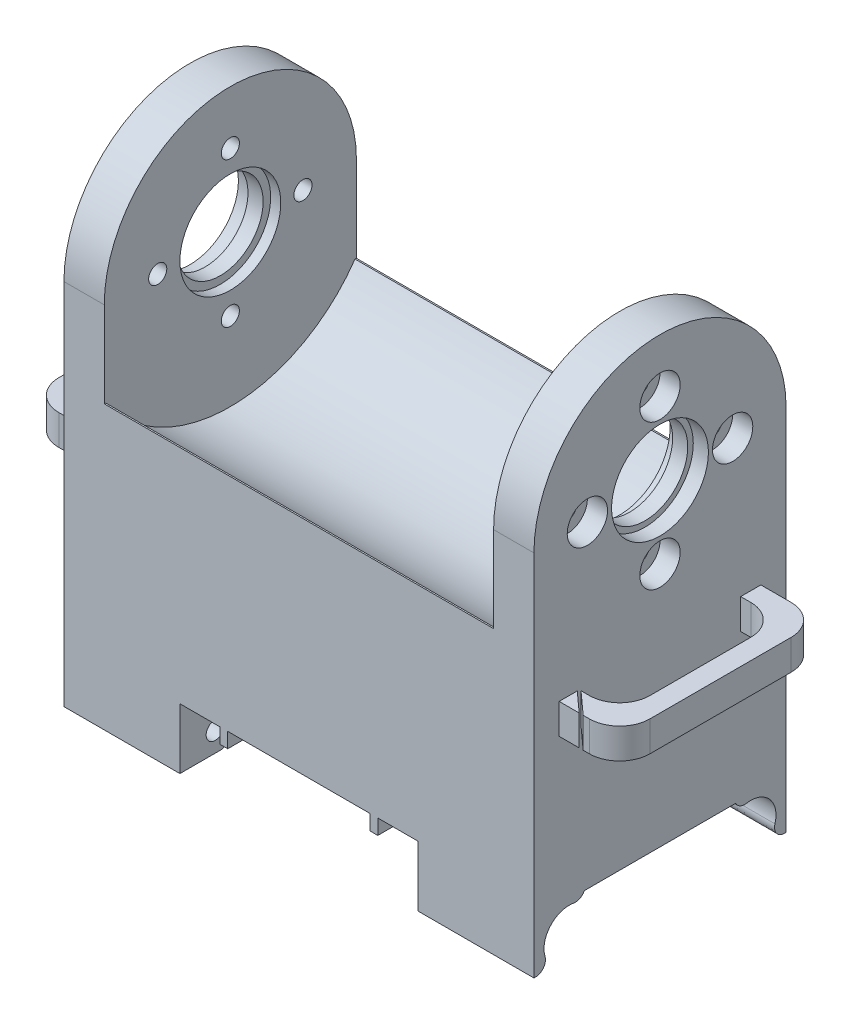
SolidWorks part; units mm, degrees
ref_plane "Front Plane" through (0, 0, 0) normal (0, 0, 1) x (1, 0, 0)
ref_plane "Top Plane" through (0, 0, 0) normal (0, 1, 0) x (1, 0, 0)
ref_plane "Right Plane" through (0, 0, 0) normal (1, 0, 0) x (0, 0, -1)
sketch "Sketch1" plane through (0, 0, 0) normal (1, 0, 0) x (0, 0, -1)
  line L0 (0, 45.2885) -> (0, -49.9038) construction
  line L1 (-47.1154, 0) -> (49.2308, 0) construction
  line L2 (-47.1154, -15) -> (49.2308, -15) construction
  line L3 (-7.5, -16) -> (7.5, -16)
  line L4 (-12.5, 28) -> (12.5, 28)
  line L5 (-12.5, 28) -> (-12.5, -21)
  line L6 (-12.5, -21) -> (-7.5, -21)
  line L7 (12.5, 28) -> (12.5, -21)
  line L8 (7.5, -21) -> (12.5, -21)
  line L9 (-7.5, -16) -> (-7.5, -21)
  line L11 (7.5, -16) -> (7.5, -21)
  point P11 (-12.5, -15)
  point P12 (-12.5, 3.5)
  dimension "D1" = 12.5
  dimension "D2" = 12.5
  dimension "D3" = 28
  dimension "D4" = 6
  dimension "D5" = 15
  dimension "D6" = 5
  dimension "D7" = 5
  dimension "D8" = 1
extrude "Boss-Extrude1" add sketch "Sketch1" along normal blind 4
sketch "Sketch3" plane through (0, 0, 0) normal (-1, 0, 0) x (0, 0, 1)
  line L0 (-12.5, -21) -> (-12.5, 28) construction
  line L1 (-12.5, -15) -> (12.5, -15)
  line L2 (-12.5, -15) -> (-12.5, 7)
  line L3 (-12.5, 7) -> (12.5, 7)
  line L4 (12.5, -15) -> (12.5, 7)
  line L5 (12.5, 28) -> (12.5, -21) construction
  line L6 (7.5, -16) -> (-7.5, -16) construction
  line L7 (-12.5, 28) -> (12.5, 28) construction
  dimension "D1" = 1
  dimension "D2" = 21
extrude "Boss-Extrude2" add sketch "Sketch3" along normal blind 19.3
fillet "Fillet1" 2 edges at (2, 28, 12.5) (2, 28, -12.5) type full round first side face at (-3.825, -0.25, 12.5) second side face at (-3.825, -0.25, -12.5) middle face at (2, 28, 0)
sketch "Sketch4" plane through (0, 0, 0) normal (-1, 0, 0) x (0, 0, 1)
  line L0 (-12.5, 15.5) -> (20.8842, 15.5) construction
  circle A0 centre (0, 15.5) radius 15
extrude "Cut-Extrude1" cut sketch "Sketch4" along normal up to next
sketch "Sketch5" plane through (4, 0, 0) normal (1, 0, 0) x (0, 0, -1)
  line L0 (-12.5, 15.5) -> (19.316, 15.5) construction
  circle A0 centre (0, 15.5) radius 4.25
  dimension "D1" = 8.5
extrude "Cut-Extrude2" cut sketch "Sketch5" against normal up to next
sketch "Sketch6" plane through (4, 0, 0) normal (1, 0, 0) x (0, 0, -1)
  circle A0 centre (0, 15.5) radius 4.8
  dimension "D1" = 9.6
extrude "Cut-Extrude3" cut sketch "Sketch6" against normal blind 1.5
sketch "Sketch7" plane through (0, 0, 0) normal (-1, 0, 0) x (0, 0, 1)
  circle A0 centre (0, 15.5) radius 5
  dimension "D1" = 10
extrude "Cut-Extrude4" cut sketch "Sketch7" against normal blind 1
sketch "Sketch8" plane through (4, 0, 0) normal (1, 0, 0) x (0, 0, -1)
  line L0 (-12.5, 15.5) -> (16.2441, 15.5) construction
  circle A0 centre (0, 22.7) radius 0.9
  dimension "D2" = 1.8
  dimension "D1" = 7.2
extrude "Cut-Extrude5" cut sketch "Sketch8" against normal up to next
pattern_circular "CirPattern1" count 4 every 90 about axis through (2.5, 15.5, 0) along (-1, 0, 0) of "Cut-Extrude5"
sketch "Sketch10" plane through (4, 0, 0) normal (1, 0, 0) x (0, 0, -1)
  circle A0 centre (0, 22.7) radius 2
extrude "Cut-Extrude6" cut sketch "Sketch10" against normal blind 2
pattern_circular "CirPattern2" count 4 every 90 about axis through (2.5, 15.5, 0) along (1, 0, 0) of "Cut-Extrude6"
sketch "Sketch11" plane through (4, 0, 0) normal (1, 0, 0) x (0, 0, -1)
  line L0 (0, -23.7409) -> (0, -4.6907) construction
  line L1 (-19.718, -19) -> (21.3022, -19) construction
  line L2 (-7.5, -16) -> (7.5, -16) construction
  circle A0 centre (-9, -19) radius 0.9
  circle A1 centre (9, -19) radius 0.9
  dimension "D4" = 1.8
  dimension "D5" = 1.8
  dimension "D1" = 3
  dimension "D2" = 9
  dimension "D3" = 9
extrude "Cut-Extrude7" cut sketch "Sketch11" against normal up to next
sketch "Sketch12" plane through (4, 0, 0) normal (1, 0, 0) x (0, 0, -1)
  circle A0 centre (-9, -19) radius 2.5
  circle A1 centre (9, -19) radius 2.5
  dimension "D1" = 5
  dimension "D2" = 5
extrude "Cut-Extrude8" cut sketch "Sketch12" against normal blind 2.5
sketch "Sketch13" plane through (0, -15, 0) normal (0, -1, 0) x (1, 0, 0)
  line L0 (-19.3, 12.5) -> (0, 12.5) construction
  line L1 (-12.2401, 12.5) -> (-11.4791, 12.5)
  line L2 (-12.2401, 12.5) -> (-12.2401, -12.5)
  line L3 (-12.2401, -12.5) -> (-11.4791, -12.5)
  line L4 (-11.4791, 12.5) -> (-11.4791, -12.5)
  line L5 (-19.3, -12.5) -> (0, -12.5) construction
extrude "Boss-Extrude3" add sketch "Sketch13" along normal blind 1.5
sketch "Sketch14" plane through (4, 0, 0) normal (1, 0, 0) x (0, 0, -1)
  line L0 (0, 3.9817) -> (0, -6.788) construction
  line L1 (-10, 1.5) -> (10, 1.5)
  line L2 (-10, 1.5) -> (-10, -1.5)
  line L3 (-10, -1.5) -> (10, -1.5)
  line L4 (10, 1.5) -> (10, -1.5)
  dimension "D1" = 10
  dimension "D2" = 10
  dimension "D3" = 3
  dimension "D4" = 1.5
extrude "Boss-Extrude4" add sketch "Sketch14" along normal blind 6
fillet "Fillet4" radius 3 2 edges at (10, 0, -10) (10, 0, 10)
sketch "Sketch15" plane through (0, -1.5, 0) normal (0, -1, 0) x (-1, 0, 0)
  line L0 (-4, -10) -> (-4, 10) construction
  line L1 (-4, -8) -> (-8, -8)
  line L2 (-4, -8) -> (-4, 8)
  line L3 (-4, 8) -> (-8, 8)
  line L4 (-8, -8) -> (-8, 8)
  line L5 (-10, -7) -> (-10, 7) construction
  line L6 (-7, 10) -> (-4, 10) construction
  line L7 (-7, -10) -> (-4, -10) construction
  point P12 (-5.5, -10)
  dimension "D1" = 2
  dimension "D2" = 2
  dimension "D3" = 2
extrude "Cut-Extrude9" cut sketch "Sketch15" against normal blind 5
fillet "Fillet5" radius 3 2 edges at (8, 0, -8) (8, 0, 8)
sketch "Sketch16" plane through (0, -1.5, 0) normal (0, -1, 0) x (-1, 0, 0)
  line L0 (-4, -8.2058) -> (-5.9892, -10)
  line L1 (-4, -10) -> (-4, -8) construction
  line L2 (-7, -10) -> (-4, -10) construction
  line L3 (-5.9892, -10) -> (-6.3838, -10)
  line L4 (-6.3838, -10) -> (-4.1665, -8)
  line L5 (-5, -8) -> (-4, -8) construction
  line L6 (-4.1665, -8) -> (-4, -8)
  line L7 (-4, -8) -> (-4, -8.2058)
extrude "Cut-Extrude10" cut sketch "Sketch16" against normal blind 5
mirror "Mirror1" about plane through (-19.3, 0, 0) normal (1, 0, 0) of bodies 116
sketch "Sketch17" plane through (0, -15, 0) normal (0, -1, 0) x (1, 0, 0)
  line L0 (-11.4791, -12.5) -> (0, -12.5) construction
  line L1 (0, 12.5) -> (-7.5, 12.5)
  line L2 (0, 12.5) -> (0, -12.5)
  line L3 (0, -12.5) -> (-7.5, -12.5)
  line L4 (-7.5, 12.5) -> (-7.5, -12.5)
  line L5 (-27.1209, 12.5) -> (-38.6, 12.5) construction
  line L6 (-38.6, -12.5) -> (-31.1, -12.5)
  line L7 (-38.6, -12.5) -> (-38.6, 12.5)
  line L8 (-38.6, 12.5) -> (-31.1, 12.5)
  line L9 (-31.1, -12.5) -> (-31.1, 12.5)
  dimension "D1" = 7.5
  dimension "D2" = 7.5
extrude "Boss-Extrude5" add sketch "Sketch17" along normal blind 6
sketch "Sketch18" plane through (1.5, 0, 0) normal (1, 0, 0) x (0, 0, -1)
  circle A0 centre (9, -19) radius 2.5
  circle A1 centre (-9, -19) radius 2.5
extrude "Cut-Extrude11" cut sketch "Sketch18" against normal blind 7.2543
sketch "Sketch19" plane through (-40.1, 0, 0) normal (-1, 0, 0) x (0, 0, 1)
  circle A0 centre (9, -19) radius 2.5
  circle A1 centre (-9, -19) radius 2.5
extrude "Cut-Extrude13" cut sketch "Sketch19" against normal blind 7.25
sketch "Sketch20" plane through (-38.6, 0, 0) normal (-1, 0, 0) x (0, 0, 1)
  line L1 (7.5, -16) -> (-7.5, -16)
  line L2 (7.5, -16) -> (7.5, -21)
  line L3 (7.5, -21) -> (-7.5, -21)
  line L4 (-7.5, -16) -> (-7.5, -21)
extrude "Cut-Extrude15" cut sketch "Sketch20" against normal through all
sketch "Sketch21" plane through (0, 0, 0) normal (1, 0, 0) x (0, 0, -1)
  circle A0 centre (-9, -19) radius 0.9
  circle A1 centre (9, -19) radius 0.9
extrude "Cut-Extrude16" cut sketch "Sketch21" against normal through all
fillet "Fillet6" radius 1 12 edges at (-37.725, -21, -10.5) (-37.725, -17, -7.5) (-31.975, -21, -7.5) (-37.725, -21, 10.5) (-37.725, -17, 7.5) (-31.975, -21, 7.5) (-6.6272, -21, 7.5) (-6.6272, -21, -7.5) (-0.8772, -17, 7.5) (-0.8772, -21, 10.5) (-0.8772, -21, -10.5) (-0.8772, -17, -7.5) first distance on face at (-35.5167, -21, -10.1667) first distance on face at (-35.5167, -18, -7.5) first distance on face at (-35.5167, -21, 10.1667) first distance on face at (-35.5167, -18, 7.5) first distance on face at (-3.0848, -21, 10.1667) first distance on face at (-3.0848, -21, -10.1667) first distance on face at (-0.8772, -18.25, 10) first distance on face at (-0.8772, -18.25, -10)
